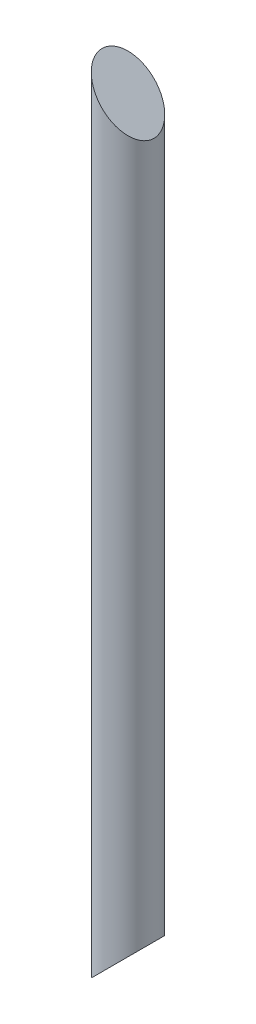
SolidWorks part; units mm, degrees
ref_plane "Front Plane" through (0, 0, 0) normal (0, 0, 1) x (1, 0, 0)
ref_plane "Top Plane" through (0, 0, 0) normal (0, 1, 0) x (1, 0, 0)
ref_plane "Right Plane" through (0, 0, 0) normal (1, 0, 0) x (0, 0, -1)
sketch "Sketch1" plane through (0, 0, 0) normal (0, 1, 0) x (1, 0, 0)
  circle A0 centre (0, 0) radius 31.75
  dimension "D1" = 63.5
extrude "Boss-Extrude3" add sketch "Sketch1" along normal blind 850.9
sketch "Sketch2" plane through (0, 0, 0) normal (0, 0, 1) x (1, 0, 0)
  line L0 (31.75, 850.9) -> (-31.75, 850.9)
  line L1 (-31.75, 850.9) -> (-31.75, 914.4)
  line L2 (-31.75, 914.4) -> (31.75, 850.9)
  line L3 (-31.75, 0) -> (31.75, 0)
  line L4 (-31.75, 0) -> (-31.75, -63.5)
  line L5 (-31.75, -63.5) -> (31.75, 0)
  line L6 (31.75, 0) -> (31.75, -63.5)
  line L7 (31.75, -63.5) -> (-31.75, -63.5)
  line L8 (31.75, 850.9) -> (31.75, 914.4)
  line L9 (31.75, 914.4) -> (-31.75, 914.4)
  dimension "D1" = 45
  dimension "D2" = 63.5
extrude "Boss-Extrude4" add sketch "Sketch1<3>" against normal blind 63.5 contours A0
sketch "Sketch1<3>" plane through (0, 0, 0) normal (0, 1, 0) x (1, 0, 0) same geometry as "Sketch1"
sketch "Sketch5" plane through (0, 850.9, 0) normal (0, 1, 0) x (1, 0, 0)
  circle A0 centre (0, 0) radius 31.75
extrude "Boss-Extrude5" add sketch "Sketch5" along normal blind 63.5
extrude "Cut-Extrude7" cut sketch "Sketch2" against normal blind 96.774 and the other way blind 96.774 contours L8 L9 L2 | L7 L6 L5 region at (10.5833, 893.2333, 0) region at (10.5833, -42.3333, 0)
